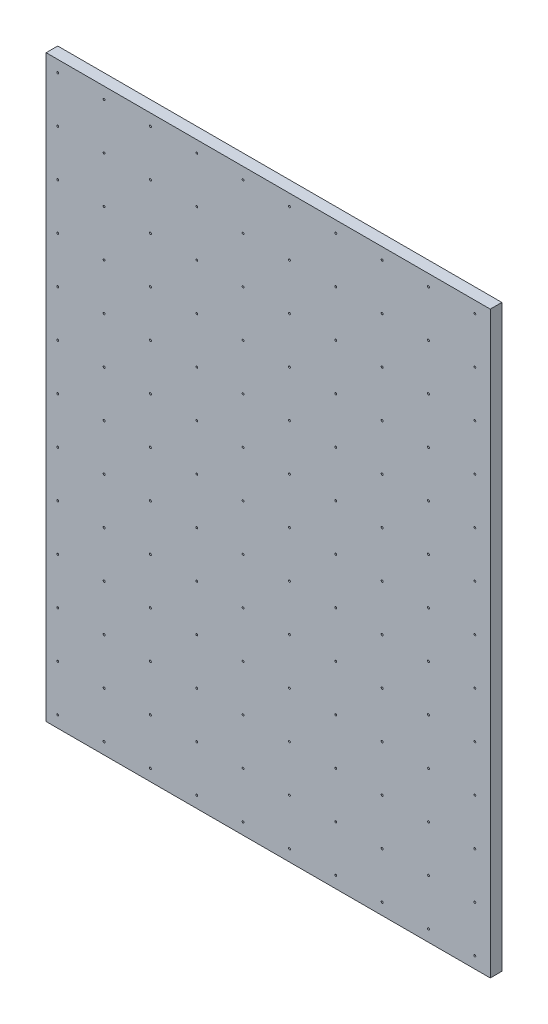
SolidWorks part; units mm, degrees
material "Фанера, берёза, ФСФ ВВ/С ГОСТ 3916.1-96"
ref_plane "Спереди" through (0, 0, 0) normal (0, 0, 1) x (1, 0, 0)
ref_plane "Сверху" through (0, 0, 0) normal (0, 1, 0) x (1, 0, 0)
ref_plane "Справа" through (0, 0, 0) normal (1, 0, 0) x (0, 0, -1)
sketch "Эскиз1" plane through (0, 0, 0) normal (0, 0, 1) x (1, 0, 0)
  line L1 (-575, 750) -> (575, 750)
  line L2 (-575, 750) -> (-575, -750)
  line L3 (-575, -750) -> (575, -750)
  line L4 (575, 750) -> (575, -750)
  line L5 (0, -750) -> (0, 750) construction
  line L6 (-575, 0) -> (575, 0) construction
  point P0 (0, 0)
  dimension "D1" = 1150
  dimension "D2" = 1500
extrude "Бобышка-Вытянуть1" add sketch "Эскиз1" along normal mid plane 30
sketch "Эскиз2" plane through (0, 0, 15) normal (0, 0, 1) x (1, 0, 0)
  line L0 (-575, 750) -> (-575, -750) construction
  line L1 (575, 750) -> (-575, 750) construction
  line L2 (-545, 720) -> (-425, 720) construction
  circle A0 centre (-545, 720) radius 2.5
  circle A1 centre (-425, 720) radius 2.5
  circle A2 centre (-305, 720) radius 2.5
  circle A3 centre (-185, 720) radius 2.5
  circle A4 centre (-65, 720) radius 2.5
  circle A5 centre (55, 720) radius 2.5
  circle A6 centre (175, 720) radius 2.5
  circle A7 centre (295, 720) radius 2.5
  circle A8 centre (415, 720) radius 2.5
  circle A9 centre (535, 720) radius 2.5
  circle A10 centre (-425, 600) radius 2.5
  circle A11 centre (-305, 600) radius 2.5
  circle A12 centre (-185, 600) radius 2.5
  circle A13 centre (-65, 600) radius 2.5
  circle A14 centre (55, 600) radius 2.5
  circle A15 centre (175, 600) radius 2.5
  circle A16 centre (295, 600) radius 2.5
  circle A17 centre (415, 600) radius 2.5
  circle A18 centre (535, 600) radius 2.5
  circle A19 centre (-425, 480) radius 2.5
  circle A20 centre (-305, 480) radius 2.5
  circle A21 centre (-185, 480) radius 2.5
  circle A22 centre (-65, 480) radius 2.5
  circle A23 centre (55, 480) radius 2.5
  circle A24 centre (175, 480) radius 2.5
  circle A25 centre (295, 480) radius 2.5
  circle A26 centre (415, 480) radius 2.5
  circle A27 centre (535, 480) radius 2.5
  circle A28 centre (-425, 360) radius 2.5
  circle A29 centre (-305, 360) radius 2.5
  circle A30 centre (-185, 360) radius 2.5
  circle A31 centre (-65, 360) radius 2.5
  circle A32 centre (55, 360) radius 2.5
  circle A33 centre (175, 360) radius 2.5
  circle A34 centre (295, 360) radius 2.5
  circle A35 centre (415, 360) radius 2.5
  circle A36 centre (535, 360) radius 2.5
  circle A37 centre (-425, 240) radius 2.5
  circle A38 centre (-305, 240) radius 2.5
  circle A39 centre (-185, 240) radius 2.5
  circle A40 centre (-65, 240) radius 2.5
  circle A41 centre (55, 240) radius 2.5
  circle A42 centre (175, 240) radius 2.5
  circle A43 centre (295, 240) radius 2.5
  circle A44 centre (415, 240) radius 2.5
  circle A45 centre (535, 240) radius 2.5
  circle A46 centre (-425, 120) radius 2.5
  circle A47 centre (-305, 120) radius 2.5
  circle A48 centre (-185, 120) radius 2.5
  circle A49 centre (-65, 120) radius 2.5
  circle A50 centre (55, 120) radius 2.5
  circle A51 centre (175, 120) radius 2.5
  circle A52 centre (295, 120) radius 2.5
  circle A53 centre (415, 120) radius 2.5
  circle A54 centre (535, 120) radius 2.5
  circle A55 centre (-425, 0) radius 2.5
  circle A56 centre (-305, 0) radius 2.5
  circle A57 centre (-185, 0) radius 2.5
  circle A58 centre (-65, 0) radius 2.5
  circle A59 centre (55, 0) radius 2.5
  circle A60 centre (175, 0) radius 2.5
  circle A61 centre (295, 0) radius 2.5
  circle A62 centre (415, 0) radius 2.5
  circle A63 centre (535, 0) radius 2.5
  circle A64 centre (-425, -120) radius 2.5
  circle A65 centre (-305, -120) radius 2.5
  circle A66 centre (-185, -120) radius 2.5
  circle A67 centre (-65, -120) radius 2.5
  circle A68 centre (55, -120) radius 2.5
  circle A69 centre (175, -120) radius 2.5
  circle A70 centre (295, -120) radius 2.5
  circle A71 centre (415, -120) radius 2.5
  circle A72 centre (535, -120) radius 2.5
  circle A73 centre (-425, -240) radius 2.5
  circle A74 centre (-305, -240) radius 2.5
  circle A75 centre (-185, -240) radius 2.5
  circle A76 centre (-65, -240) radius 2.5
  circle A77 centre (55, -240) radius 2.5
  circle A78 centre (175, -240) radius 2.5
  circle A79 centre (295, -240) radius 2.5
  circle A80 centre (415, -240) radius 2.5
  circle A81 centre (535, -240) radius 2.5
  circle A82 centre (-425, -360) radius 2.5
  circle A83 centre (-305, -360) radius 2.5
  circle A84 centre (-185, -360) radius 2.5
  circle A85 centre (-65, -360) radius 2.5
  circle A86 centre (55, -360) radius 2.5
  circle A87 centre (175, -360) radius 2.5
  circle A88 centre (295, -360) radius 2.5
  circle A89 centre (415, -360) radius 2.5
  circle A90 centre (535, -360) radius 2.5
  circle A91 centre (-425, -480) radius 2.5
  circle A92 centre (-305, -480) radius 2.5
  circle A93 centre (-185, -480) radius 2.5
  circle A94 centre (-65, -480) radius 2.5
  circle A95 centre (55, -480) radius 2.5
  circle A96 centre (175, -480) radius 2.5
  circle A97 centre (295, -480) radius 2.5
  circle A98 centre (415, -480) radius 2.5
  circle A99 centre (535, -480) radius 2.5
  circle A100 centre (-425, -600) radius 2.5
  circle A101 centre (-305, -600) radius 2.5
  circle A102 centre (-185, -600) radius 2.5
  circle A103 centre (-65, -600) radius 2.5
  circle A104 centre (55, -600) radius 2.5
  circle A105 centre (175, -600) radius 2.5
  circle A106 centre (295, -600) radius 2.5
  circle A107 centre (415, -600) radius 2.5
  circle A108 centre (535, -600) radius 2.5
  circle A109 centre (-425, -720) radius 2.5
  circle A110 centre (-305, -720) radius 2.5
  circle A111 centre (-185, -720) radius 2.5
  circle A112 centre (-65, -720) radius 2.5
  circle A113 centre (55, -720) radius 2.5
  circle A114 centre (175, -720) radius 2.5
  circle A115 centre (295, -720) radius 2.5
  circle A116 centre (415, -720) radius 2.5
  circle A117 centre (535, -720) radius 2.5
  circle A118 centre (-545, 600) radius 2.5
  circle A119 centre (-545, 480) radius 2.5
  circle A120 centre (-545, 360) radius 2.5
  circle A121 centre (-545, 240) radius 2.5
  circle A122 centre (-545, 120) radius 2.5
  circle A123 centre (-545, 0) radius 2.5
  circle A124 centre (-545, -120) radius 2.5
  circle A125 centre (-545, -240) radius 2.5
  circle A126 centre (-545, -360) radius 2.5
  circle A127 centre (-545, -480) radius 2.5
  circle A128 centre (-545, -600) radius 2.5
  circle A129 centre (-545, -720) radius 2.5
  dimension "D1" = 5
  dimension "D2" = 30
  dimension "D3" = 30
  dimension "D6" = 120
  dimension "D4" = 10
  dimension "D5" = 13
extrude "Вырез-Вытянуть1" cut sketch "Эскиз2" against normal through all
equation "\"ширина 1-я панель\"=1150"
equation "\"длина 1-я панель\"=1500"
equation "\"толщина дсп\"=30"
equation "\"D1@Эскиз1\"=\"ширина 1-я панель\""
equation "\"D2@Эскиз1\"=\"длина 1-я панель\""
equation "\"D3@Эскиз2\"=\"D2@Эскиз2\""
